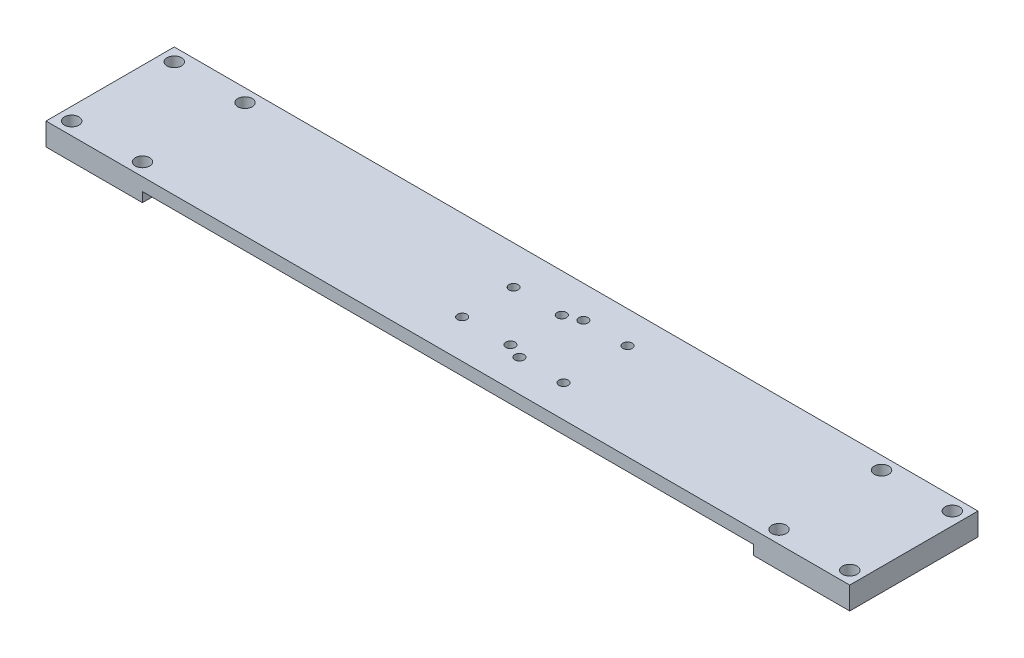
SolidWorks part; units mm, degrees
ref_plane "前视基准面" through (0, 0, 0) normal (0, 0, 1) x (1, 0, 0)
ref_plane "上视基准面" through (0, 0, 0) normal (0, 1, 0) x (1, 0, 0)
ref_plane "右视基准面" through (0, 0, 0) normal (1, 0, 0) x (0, 0, -1)
other "Configuration Table"
sketch "草图1" plane through (0, 0, 0) normal (0, 1, 0) x (1, 0, 0)
  line L1 (0, 0) -> (-250, 0)
  line L2 (0, 0) -> (0, 39.9)
  line L3 (0, 39.9) -> (-250, 39.9)
  line L4 (-250, 0) -> (-250, 39.9)
  dimension "D1" = 39.9
  dimension "D2" = 250
extrude "凸台-拉伸1" add sketch "草图1" along normal blind 4
sketch "草图2" plane through (0, 4, 0) normal (0, 1, 0) x (1, 0, 0)
  line L0 (0, 39.9) -> (-250, 39.9) construction
  line L1 (-135, 39.9) -> (-115, 39.9) construction
  line L2 (-135, 39.9) -> (-135, 0) construction
  line L3 (-135, 0) -> (-115, 0) construction
  line L4 (-115, 39.9) -> (-115, 0) construction
  line L5 (-250, 0) -> (0, 0) construction
  line L6 (-250, 39.9) -> (-250, 0) construction
  line L7 (-135, 39.9) -> (-132.5, 39.9) construction
  line L8 (-132.5, 39.9) -> (-132.5, 27.95) construction
  line L9 (-132.5, 27.95) -> (-132.5, 11.95) construction
  line L10 (-132.5, 11.95) -> (-117.5, 11.95) construction
  line L11 (-117.5, 11.95) -> (-117.5, 27.95) construction
  circle A0 centre (-132.5, 27.95) radius 1.45
  circle A1 centre (-117.5, 27.95) radius 1.45
  circle A2 centre (-117.5, 11.95) radius 1.45
  circle A3 centre (-132.5, 11.95) radius 1.45
  dimension "D8" = 2.9
  dimension "D9" = 2.9
  dimension "D10" = 2.9
  dimension "D11" = 2.9
  dimension "D1" = 20
  dimension "D2" = 115
  dimension "D3" = 2.5
  dimension "D4" = 11.95
  dimension "D5" = 16
  dimension "D6" = 15
  dimension "D7" = 16
extrude "切除-拉伸1" cut sketch "草图2" against normal blind 12
extrude "切除-拉伸2" cut sketch "草图3" against normal blind 12
sketch "草图3" plane through (-275.0918, 0, 148.8475) normal (0, -1, 0) x (-1, 0, 0.0018)
  circle A4 centre (-162.6339, 158.5484) radius 1.45
  circle A5 centre (-162.6706, 178.4484) radius 1.45
  circle A6 centre (-176.3839, 158.5231) radius 1.45
  circle A7 centre (-176.4206, 178.423) radius 1.45
sketch "草图7" plane through (0, 4, 0) normal (0, 1, 0) x (1, 0, 0)
  line L0 (-250, 39.9) -> (-246, 39.9) construction
  line L1 (0, 39.9) -> (-250, 39.9) construction
  line L2 (-246, 39.9) -> (-246, 35.9) construction
  line L3 (-246, 35.9) -> (-224, 35.9) construction
  line L4 (-250, 19.95) -> (-131.5357, 19.95) construction
  line L5 (-250, 39.9) -> (-250, 0) construction
  line L6 (-125, 39.9) -> (-125, 25.1167) construction
  line L7 (0, 19.95) -> (-118.4643, 19.95) construction
  line L8 (-4, 35.9) -> (-26, 35.9) construction
  line L9 (-4, 39.9) -> (-4, 35.9) construction
  line L10 (0, 39.9) -> (-4, 39.9) construction
  circle A0 centre (-246, 35.9) radius 2.25
  circle A1 centre (-224, 35.9) radius 2.25
  circle A2 centre (-224, 4) radius 2.25
  circle A3 centre (-246, 4) radius 2.25
  circle A4 centre (-4, 4) radius 2.25
  circle A5 centre (-26, 4) radius 2.25
  circle A6 centre (-26, 35.9) radius 2.25
  circle A7 centre (-4, 35.9) radius 2.25
  dimension "D4" = 4.5
  dimension "D5" = 4.5
  dimension "D1" = 4
  dimension "D2" = 4
  dimension "D3" = 22
extrude "切除-拉伸6" cut sketch "草图7" against normal blind 20
sketch "草图8" plane through (0, 0, 0) normal (0, -1, 0) x (1, 0, 0)
  line L0 (0, -39.9) -> (-250, -39.9) construction
  line L1 (-250, 0) -> (-220, 0)
  line L2 (-250, 0) -> (-250, -39.9)
  line L3 (-250, -39.9) -> (-220, -39.9)
  line L4 (-220, 0) -> (-220, -39.9)
  line L6 (0, 0) -> (-30, 0)
  line L7 (0, 0) -> (0, -39.9)
  line L8 (0, -39.9) -> (-30, -39.9)
  line L9 (-30, 0) -> (-30, -39.9)
  circle A0 centre (-4, -35.9) radius 2.25 construction
  circle A1 centre (-26, -35.9) radius 2.25 construction
  circle A2 centre (-4, -4) radius 2.25 construction
  circle A3 centre (-26, -4) radius 2.25 construction
  circle A4 centre (-224, -35.9) radius 2.25 construction
  circle A5 centre (-246, -35.9) radius 2.25 construction
  circle A6 centre (-224, -4) radius 2.25 construction
  circle A7 centre (-246, -4) radius 2.25 construction
  circle A8 centre (-4, -35.9) radius 2.25
  circle A9 centre (-26, -35.9) radius 2.25
  circle A10 centre (-4, -4) radius 2.25
  circle A11 centre (-26, -4) radius 2.25
  circle A12 centre (-224, -35.9) radius 2.25
  circle A13 centre (-246, -35.9) radius 2.25
  circle A14 centre (-224, -4) radius 2.25
  circle A15 centre (-246, -4) radius 2.25
  dimension "D1" = 30
  dimension "D2" = 30
extrude "凸台-拉伸2" add sketch "草图8" along normal blind 1
sketch "草图9" plane through (0, -1, 0) normal (0, -1, 0) x (1, 0, 0)
  line L0 (0, -39.9) -> (0, 0) construction
  line L1 (0, 0) -> (-30, 0) construction
  line L2 (-30, 0) -> (-30, -39.9) construction
  line L3 (-30, -39.9) -> (0, -39.9) construction
  line L4 (-250, 0) -> (-250, -39.9) construction
  line L5 (-250, -39.9) -> (-220, -39.9) construction
  line L6 (-220, -39.9) -> (-220, 0) construction
  line L7 (-220, 0) -> (-250, 0) construction
  line L8 (0, -39.9) -> (0, 0)
  line L9 (0, 0) -> (-30, 0)
  line L10 (-30, 0) -> (-30, -39.9)
  line L11 (-30, -39.9) -> (0, -39.9)
  line L12 (-250, 0) -> (-250, -39.9)
  line L13 (-250, -39.9) -> (-220, -39.9)
  line L14 (-220, -39.9) -> (-220, 0)
  line L15 (-220, 0) -> (-250, 0)
extrude "凸台-拉伸3" add sketch "草图9" along normal blind 2
sketch "草图10" plane through (0, -1, 0) normal (0, 1, 0) x (1, 0, 0)
  circle A0 centre (-246, 35.9) radius 1.5
  circle A1 centre (-246, 4) radius 1.5
  circle A2 centre (-224, 35.9) radius 1.5
  circle A3 centre (-224, 4) radius 1.5
  circle A4 centre (-26, 35.9) radius 1.5
  circle A5 centre (-26, 4) radius 1.5
  circle A6 centre (-4, 35.9) radius 1.5
  circle A7 centre (-4, 4) radius 1.5
  dimension "D1" = 3
extrude "切除-拉伸7" cut sketch "草图10" against normal blind 3
